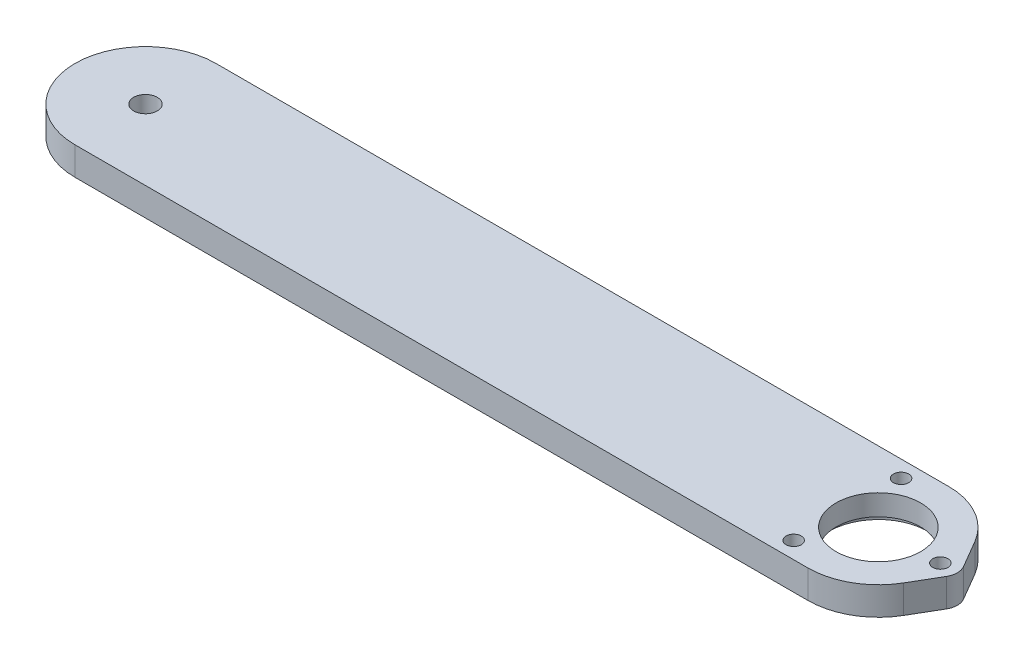
SolidWorks part; units mm, degrees
ref_plane "前视基准面" through (0, 0, 0) normal (0, 0, 1) x (1, 0, 0)
ref_plane "上视基准面" through (0, 0, 0) normal (0, 1, 0) x (1, 0, 0)
ref_plane "右视基准面" through (0, 0, 0) normal (1, 0, 0) x (0, 0, -1)
sketch "草图1" plane through (0, 0, 0) normal (0, 1, 0) x (1, 0, 0)
  line L0 (-65, 0) -> (65, 0) construction
  line L1 (-65, 12.5) -> (65, 12.5)
  line L2 (-65, -12.5) -> (65, -12.5)
  arc A0 (-65, 12.5) -> (-65, -12.5) centre (-65, 0) ccw
  arc A1 (65, -12.5) -> (65, 12.5) centre (65, 0) ccw
  point P2 (0, 0)
  dimension "D2" = 12.5
  dimension "D1" = 130
extrude "凸台-拉伸1" add sketch "草图1" along normal blind 5
sketch "草图10" plane through (0, 0, 0) normal (0, -1, 0) x (1, 0, 0)
  line L0 (75.7955, -6.3014) -> (78.5909, -1.5123)
  line L3 (75.7955, 6.3014) -> (78.5909, 1.5123)
  line L4 (75.7955, -6.3014) -> (75.7955, 6.3014)
  line L5 (76, 0) -> (77.5, 0) construction
  circle A5 centre (76, 0) radius 3 construction
  arc A6 (65, -12.5) -> (65, 12.5) centre (65, 0) ccw construction
  arc A7 (78.5909, -1.5123) -> (78.5909, 1.5123) centre (76, 0) ccw
  dimension "D1" = 6
  dimension "D2" = 1.5
extrude "凸台-拉伸5" add sketch "草图10" against normal up to surface (5 mm away) up to face at (0, 5, 0)
sketch "草图7" plane through (0, 5, 0) normal (0, 1, 0) x (1, 0, 0)
  circle A0 centre (65, 0) radius 7.5
  dimension "D1" = 15
extrude "切除-拉伸2" cut sketch "草图7" against normal up to next
sketch "草图8" plane through (0, 0, 0) normal (0, 1, 0) x (1, 0, 0)
  circle A0 centre (65, 0) radius 8.75
  dimension "D1" = 17.5
extrude "切除-拉伸3" cut sketch "草图8" along normal blind 1.3
sketch "草图9" plane through (0, 0, 0) normal (0, -1, 0) x (1, 0, 0)
  line L0 (65, 0) -> (54, 0) construction
  line L1 (65, 0) -> (59.5, 9.5263) construction
  circle A0 centre (65, 0) radius 11 construction
  circle A5 centre (59.5, 9.5263) radius 1.35
  circle A9 centre (76, 0) radius 1.35
  circle A10 centre (59.5, -9.5263) radius 1.35
  point P12 (65, 0)
  point P15 (65, 0)
  dimension "22" = 22
  dimension "D3" = 2.7
  dimension "D2" = 60
  dimension "D1" = 3
extrude "切除-拉伸4" cut sketch "草图9" against normal up to next
sketch "草图12" plane through (0, 5, 0) normal (0, 1, 0) x (1, 0, 0)
  circle A0 centre (-65, 0) radius 2.1
  dimension "D1" = 4.2
extrude "切除-拉伸5" cut sketch "草图12" against normal up to next
sketch "草图13" plane through (0, 0, 0) normal (0, -1, 0) x (1, 0, 0)
  circle A0 centre (59.5, 9.5263) radius 2.75
  circle A1 centre (76, 0) radius 2.75
  circle A2 centre (59.5, -9.5263) radius 2.75
  dimension "D1" = 5.5
sketch "草图14" plane through (0, 0, 0) normal (0, -1, 0) x (1, 0, 0)
  line L0 (65, -12.5) -> (-65, -12.5) construction
  line L1 (-52, -12.5) -> (-12, -12.5)
  line L2 (-52, -12.5) -> (-52, -5.5)
  line L3 (-52, -5.5) -> (-12, -5.5)
  line L4 (-12, -12.5) -> (-12, -5.5)
  dimension "D1" = 7
  dimension "D2" = 40
  dimension "D3" = 13
extrude "凸台-拉伸6" add sketch "草图14" along normal blind 15
chamfer "倒角1" distance 7 distance2 3 1 edges at (-52, -7.5, -5.5) first distance on face at (-32, -7.5, -5.5)
sketch "草图15" plane through (-52, 0, 0) normal (-1, 0, 0) x (0, 0, 1)
  line L0 (-5.5, -12.5) -> (-4.5, -12.5) construction
  line L1 (-5.5, 0) -> (-5.5, -15) construction
  line L2 (-5.5, -15) -> (-8.5, -15) construction
  circle A0 centre (-4.5, -12.5) radius 2
  dimension "D2" = 4
  dimension "D1" = 1
  dimension "D3" = 2.5
extrude "切除-拉伸6" cut sketch "草图15" against normal up to next
fillet "圆角3" radius 2 6 edges at (-52, -7.5, -8.5) (-52, -7.5, -12.5) (-45, -14.616, -5.5) (-45, -5.384, -5.5) (-12, -5.384, -5.5) (-12, -7.5, -12.5)
chamfer "倒角2" distance 5 angle 45 9 edges at (-51.4142, 0, -11.9142) (-52, 0, -10.1594) (-12.5858, 0, -11.9142) (-51.6697, 0, -8.7178) (-12, 0, -9) (-48.0826, 0, -6.8211) (-12.5858, 0, -6.0858) (-44.9916, 0, -5.5408) (-29.2947, 0, -5.5)
sketch "草图16" plane through (0, -15, 0) normal (0, -1, 0) x (1, 0, 0)
  line L0 (-61.3333, -12.5) -> (-33.3333, -0.5)
  line L1 (-56.7082, -12.5) -> (-65, -12.5) construction
  line L2 (-44.5895, -0.5) -> (-14, -0.5) construction
  line L3 (-33.3333, -0.5) -> (-61.3333, -0.5)
  line L4 (-61.3333, -0.5) -> (-61.3333, -12.5)
  line L5 (-45.3773, -5.6617) -> (-50.7878, -7.9805) construction
extrude "切除-拉伸7" cut sketch "草图16" against normal up to surface (15 mm away) up to face at (-2.8835, 0, -3.698)
